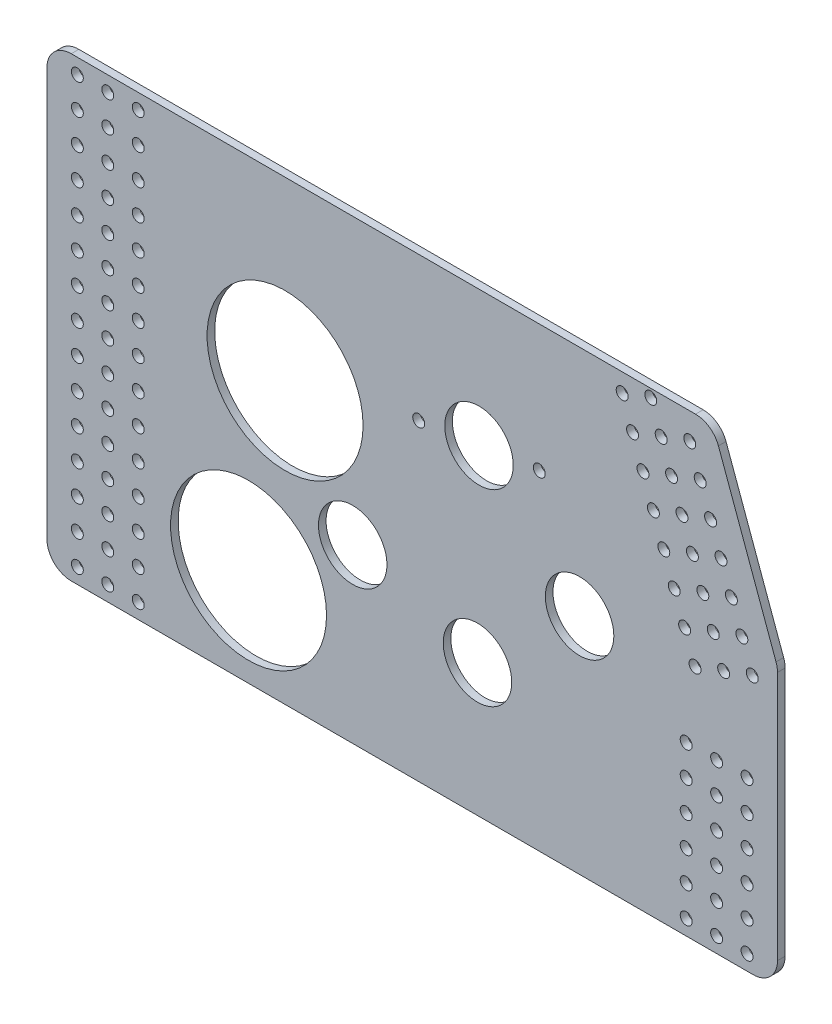
SolidWorks part; units mm, degrees
ref_plane "Front Plane" through (0, 0, 0) normal (0, 0, 1) x (1, 0, 0)
ref_plane "Top Plane" through (0, 0, 0) normal (0, 1, 0) x (1, 0, 0)
ref_plane "Right Plane" through (0, 0, 0) normal (1, 0, 0) x (0, 0, -1)
sketch "Sketch1" plane through (0, 0, 0) normal (0, 0, 1) x (1, 0, 0)
  line B0 (-152.4, 0) -> (152.4, 0)
  line B1 (152.4, 0) -> (152.4, 116.0843)
  line B2 (152.4, 116.0843) -> (125.3149, 190.5)
  line B3 (125.3149, 190.5) -> (-152.4, 190.5)
  line B4 (-152.4, 190.5) -> (-152.4, 0)
  circle B5 centre (-139.7, 184.15) radius 2.4892
  circle B6 centre (-127, 184.15) radius 2.4892
  circle B7 centre (-114.3, 184.15) radius 2.4892
  circle B8 centre (-127, 171.45) radius 2.4892
  circle B9 centre (-114.3, 171.45) radius 2.4892
  circle B10 centre (-127, 158.75) radius 2.4892
  circle B11 centre (-114.3, 158.75) radius 2.4892
  circle B12 centre (-127, 146.05) radius 2.4892
  circle B13 centre (-114.3, 146.05) radius 2.4892
  circle B14 centre (-127, 133.35) radius 2.4892
  circle B15 centre (-114.3, 133.35) radius 2.4892
  circle B16 centre (-127, 120.65) radius 2.4892
  circle B17 centre (-114.3, 120.65) radius 2.4892
  circle B18 centre (-127, 107.95) radius 2.4892
  circle B19 centre (-114.3, 107.95) radius 2.4892
  circle B20 centre (-127, 95.25) radius 2.4892
  circle B21 centre (-114.3, 95.25) radius 2.4892
  circle B22 centre (-127, 82.55) radius 2.4892
  circle B23 centre (-114.3, 82.55) radius 2.4892
  circle B24 centre (-127, 69.85) radius 2.4892
  circle B25 centre (-114.3, 69.85) radius 2.4892
  circle B26 centre (-127, 57.15) radius 2.4892
  circle B27 centre (-114.3, 57.15) radius 2.4892
  circle B28 centre (-127, 44.45) radius 2.4892
  circle B29 centre (-114.3, 44.45) radius 2.4892
  circle B30 centre (-127, 31.75) radius 2.4892
  circle B31 centre (-114.3, 31.75) radius 2.4892
  circle B32 centre (-127, 19.05) radius 2.4892
  circle B33 centre (-114.3, 19.05) radius 2.4892
  circle B34 centre (-127, 6.35) radius 2.4892
  circle B35 centre (-114.3, 6.35) radius 2.4892
  circle B36 centre (-139.7, 171.45) radius 2.4892
  circle B37 centre (-139.7, 158.75) radius 2.4892
  circle B38 centre (-139.7, 146.05) radius 2.4892
  circle B39 centre (-139.7, 133.35) radius 2.4892
  circle B40 centre (-139.7, 120.65) radius 2.4892
  circle B41 centre (-139.7, 107.95) radius 2.4892
  circle B42 centre (-139.7, 95.25) radius 2.4892
  circle B43 centre (-139.7, 82.55) radius 2.4892
  circle B44 centre (-139.7, 69.85) radius 2.4892
  circle B45 centre (-139.7, 57.15) radius 2.4892
  circle B46 centre (-139.7, 44.45) radius 2.4892
  circle B47 centre (-139.7, 31.75) radius 2.4892
  circle B48 centre (-139.7, 19.05) radius 2.4892
  circle B49 centre (-139.7, 6.35) radius 2.4892
  circle B50 centre (87.5907, 182.7494) radius 2.4892
  circle B51 centre (99.5248, 187.093) radius 2.4892
  circle B52 centre (115.8026, 179.5026) radius 2.4892
  circle B53 centre (91.9344, 170.8153) radius 2.4892
  circle B54 centre (103.8685, 175.1589) radius 2.4892
  circle B55 centre (120.1462, 167.5685) radius 2.4892
  circle B56 centre (96.278, 158.8812) radius 2.4892
  circle B57 centre (108.2121, 163.2248) radius 2.4892
  circle B58 centre (124.4899, 155.6344) radius 2.4892
  circle B59 centre (100.6217, 146.9471) radius 2.4892
  circle B60 centre (112.5558, 151.2907) radius 2.4892
  circle B61 centre (128.8335, 143.7003) radius 2.4892
  circle B62 centre (104.9653, 135.013) radius 2.4892
  circle B63 centre (116.8994, 139.3566) radius 2.4892
  circle B64 centre (133.1772, 131.7662) radius 2.4892
  circle B65 centre (109.309, 123.0789) radius 2.4892
  circle B66 centre (121.2431, 127.4226) radius 2.4892
  circle B67 centre (137.5208, 119.8321) radius 2.4892
  circle B68 centre (113.6526, 111.1448) radius 2.4892
  circle B69 centre (125.5867, 115.4885) radius 2.4892
  circle B70 centre (141.8645, 107.898) radius 2.4892
  circle B71 centre (117.9963, 99.2107) radius 2.4892
  circle B72 centre (129.9304, 103.5544) radius 2.4892
  circle B73 centre (146.2081, 95.9639) radius 2.4892
  circle B74 centre (114.3, 69.85) radius 2.4892
  circle B75 centre (127, 69.85) radius 2.4892
  circle B76 centre (139.7, 69.85) radius 2.4892
  circle B77 centre (114.3, 57.15) radius 2.4892
  circle B78 centre (127, 57.15) radius 2.4892
  circle B79 centre (139.7, 57.15) radius 2.4892
  circle B80 centre (114.3, 44.45) radius 2.4892
  circle B81 centre (127, 44.45) radius 2.4892
  circle B82 centre (139.7, 44.45) radius 2.4892
  circle B83 centre (114.3, 31.75) radius 2.4892
  circle B84 centre (127, 31.75) radius 2.4892
  circle B85 centre (139.7, 31.75) radius 2.4892
  circle B86 centre (114.3, 19.05) radius 2.4892
  circle B87 centre (127, 19.05) radius 2.4892
  circle B88 centre (139.7, 19.05) radius 2.4892
  circle B89 centre (114.3, 6.35) radius 2.4892
  circle B90 centre (127, 6.35) radius 2.4892
  circle B91 centre (139.7, 6.35) radius 2.4892
  circle B92 centre (11.8508, 132.0168) radius 14.2875
  circle B93 centre (-24.8197, 71.7449) radius 14.2875
  circle B94 centre (57.6351, 95.7125) radius 14.2875
  circle B95 centre (23.7546, 49.6787) radius 14.2875
  circle B96 centre (-65.2702, 36.9534) radius 29.9974
  circle B97 centre (-65.2702, 106.5494) radius 29.9974
  circle B98 centre (-7.8935, 147.9957) radius 2.4892
  circle B99 centre (31.595, 116.038) radius 2.4892
  circle B100 centre (5.6698, 80.2095) radius 2.4892
  circle B101 centre (41.8394, 80.2095) radius 2.4892
  circle B102 centre (41.8394, 19.1479) radius 2.4892
  circle B103 centre (5.6698, 19.1479) radius 2.4892
sketch_block_instance "Block-OuterPlate-1"
sketch_block "Block-OuterPlate" parameters "D1"=4.9784, "D7"=4.9784, "D8"=4.9784, "D9"=4.9784, "D11"=4.9784, "D12"=4.9784, "D13"=4.9784, "D15"=59.9948, "D16"=59.9948, "D17"=28.575, "D18"=28.575, "D19"=28.575, "D20"=28.575, "D21"=4.9784, "D22"=4.9784, "D23"=4.9784, "D24"=4.9784, "D25"=4.9784, "D26"=4.9784, "D2"=6.35, "D3"=12.7, "D4"=12.7, "D5"=12.7, "D6"=6.35, "D10"=12.7, "D14"=12.7, "D27"=36.1696, "D28"=18.0848, "D29"=30.5308, "D30"=30.5308
extrude "Boss-Extrude1" add sketch "Sketch1" along normal blind 3.175
sketch "Sketch2" plane through (0, 0, 3.175) normal (0, 0, 1) x (1, 0, 0)
  circle A0 centre (146.2081, 95.9639) radius 2.4892
  dimension "D1" = 4.9784
extrude "Boss-Extrude2" add sketch "Sketch2" against normal blind 3.175
fillet "Fillet1" radius 10.16 5 edges at (-152.4, 0, 1.5875) (152.4, 0, 1.5875) (152.4, 116.0843, 1.5875) (125.3149, 190.5, 1.5875) (-152.4, 190.5, 1.5875)
sketch "Sketch7" plane through (0, 0, 3.175) normal (0, 0, 1) x (1, 0, 0)
  circle A0 centre (11.8508, 132.0168) radius 14.2875 construction
  circle A1 centre (57.6351, 95.7125) radius 14.2875 construction
  circle A2 centre (23.7546, 49.6787) radius 14.2875 construction
  circle A3 centre (11.8508, 132.0168) radius 14.2875
  circle A4 centre (57.6351, 95.7125) radius 14.2875
  circle A5 centre (23.7546, 49.6787) radius 14.2875
  circle A6 centre (41.8394, 19.1479) radius 2.4892 construction
  circle A7 centre (5.6698, 19.1479) radius 2.4892 construction
  circle A8 centre (-7.8935, 147.9957) radius 2.4892 construction
  circle A9 centre (31.595, 116.038) radius 2.4892 construction
  circle A10 centre (41.8394, 80.2095) radius 2.4892 construction
  circle A11 centre (5.6698, 80.2095) radius 2.4892 construction
  circle A12 centre (41.8394, 19.1479) radius 2.4892
  circle A13 centre (5.6698, 19.1479) radius 2.4892
  circle A14 centre (-7.8935, 147.9957) radius 2.4892
  circle A15 centre (31.595, 116.038) radius 2.4892
  circle A16 centre (41.8394, 80.2095) radius 2.4892
  circle A17 centre (5.6698, 80.2095) radius 2.4892
extrude "Boss-Extrude4" add sketch "Sketch7" against normal up to surface (3.175 mm away) up to face at (25.4598, 99.6963, 0)
sketch "Sketch8" plane through (0, 0, 3.175) normal (0, 0, 1) x (1, 0, 0)
  line L0 (2.7114, 130.4399) -> (53.017, 137.5099) construction
  line L1 (27.8642, 133.9749) -> (2.7114, 133.9749) construction
  line L2 (2.7114, 130.4399) -> (2.7114, 133.9749) construction
  circle A0 centre (-24.8197, 71.7449) radius 14.2875 construction
  circle A1 centre (-24.8197, 71.7449) radius 14.2875
  circle A2 centre (-24.8197, 71.7449) radius 13.97
  circle A3 centre (27.2348, 55.2349) radius 40.64
  circle A4 centre (27.2348, 55.2349) radius 14.2875
  circle A5 centre (27.2348, 55.2349) radius 22.86
  circle A6 centre (69.8319, 93.3349) radius 34.29
  circle A7 centre (69.8319, 93.3349) radius 14.2875
  circle A8 centre (69.8319, 93.3349) radius 12.7
  circle A9 centre (27.8642, 133.9749) radius 45.72
  circle A10 centre (27.8642, 133.9749) radius 14.2875
  circle A11 centre (53.017, 137.5099) radius 2.4892
  circle A12 centre (2.7114, 130.4399) radius 2.4892
  dimension "D1" = 27.94
  dimension "D2" = 81.28
  dimension "D3" = 28.575
  dimension "D4" = 45.72
  dimension "D5" = 68.58
  dimension "D6" = 28.575
  dimension "D7" = 25.4
  dimension "D8" = 91.44
  dimension "D12" = 28.575
  dimension "D13" = 50.8
  dimension "D14" = 4.9784
  dimension "D9" = 16.51
  dimension "D10" = 38.1
  dimension "D11" = 40.64
  dimension "D15" = 8
extrude "Cut-Extrude1" cut sketch "Sketch8" against normal through all contours A4 | A8 | A9 A7 A8 | A10 | A7 A9 | A12 | A11 region at (69.8319, 93.3349, 3.175) region at (58.9004, 99.8547, 3.175) region at (60.198, 102.664, 3.175) region at (27.2348, 55.2349, 3.175) region at (27.8642, 133.9749, 3.175) region at (53.017, 137.5099, 3.175) region at (2.7114, 130.4399, 3.175)
sketch "Sketch11" plane through (0, 0, 3.175) normal (0, 0, 1) x (1, 0, 0)
  circle A0 centre (-65.2702, 36.9534) radius 29.9974 construction
  circle A1 centre (-65.2702, 106.5494) radius 29.9974 construction
  circle A2 centre (-65.2702, 36.9534) radius 29.9974
  circle A3 centre (-65.2702, 106.5494) radius 29.9974
extrude "Boss-Extrude5" add sketch "Sketch11" against normal up to surface (3.175 mm away) up to face at (41.5223, 55.2349, 0)
sketch "Sketch10" plane through (0, 0, 3.175) normal (0, 0, 1) x (1, 0, 0)
  circle A0 centre (-24.8197, 71.7449) radius 14.2875 construction
  circle A1 centre (-24.8197, 71.7449) radius 14.2875
  circle A2 centre (-24.8197, 71.7449) radius 45.72
  circle A3 centre (-53.0343, 117.0118) radius 7.62
  circle A5 centre (-68.2743, 40.8118) radius 7.62
  circle A6 centre (-53.0343, 117.0118) radius 32.5374
  circle A8 centre (-68.2743, 40.8118) radius 32.5374
  dimension "D1" = 91.44
  dimension "D2" = 15.24
  dimension "D5" = 65.0748
  dimension "D6" = 65.0748
  dimension "D3" = 76.2
  dimension "D4" = 15.24
extrude "Cut-Extrude2" cut sketch "Sketch10" against normal through all contours A2 A8 A5 | A2 A8 | A2 A6 A3 | A2 A6 | A3 | A5 region at (-42.6521, 100.3548, 3.175) region at (-53.0343, 117.0118, 3.175) region at (-57.6271, 124.3804, 3.175) region at (-68.2743, 40.8118, 3.175) region at (-75.3479, 35.7764, 3.175) region at (-52.2842, 52.1943, 3.175)
